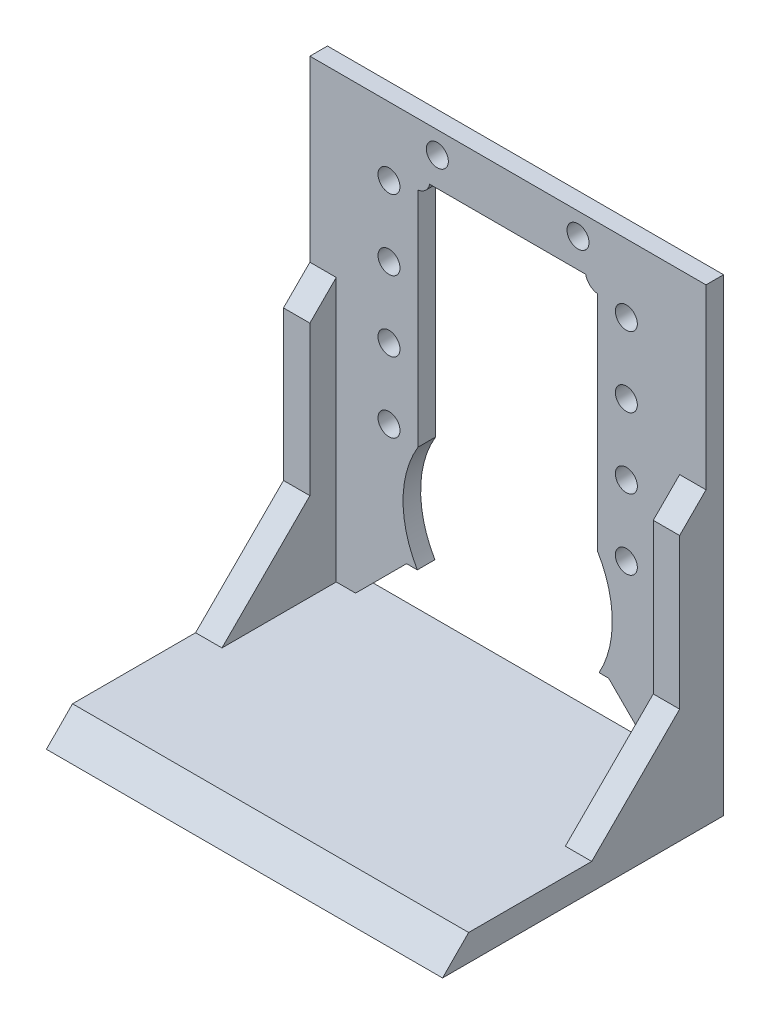
SolidWorks part; units mm, degrees
ref_plane "Płaszczyzna przednia" through (0, 0, 0) normal (0, 0, 1) x (1, 0, 0)
ref_plane "Płaszczyzna górna" through (0, 0, 0) normal (0, 1, 0) x (1, 0, 0)
ref_plane "Płaszczyzna prawa" through (0, 0, 0) normal (1, 0, 0) x (0, 0, -1)
sketch "Szkic2" plane through (0, 0, 0) normal (0, 0, 1) x (1, 0, 0)
  line L0 (-303.4601, 62.9953) -> (-191.4601, 62.9953)
  line L1 (-212.7368, 18.4953) -> (-237.0601, 18.7117)
  line L2 (-257.7368, 18.4953) -> (-282.1834, 18.4953)
  line L56 (-211.3394, 57.1953) -> (-193.5808, 57.1953)
  line L57 (-192.2601, 55.9583) -> (-192.2601, 30.6247)
  line L58 (-192.1834, 18.4953) -> (-191.4601, 18.4953)
  line L59 (-191.4601, 18.4953) -> (-186.4601, 23.4953)
  line L60 (-186.4601, 23.4953) -> (-186.4601, 57.9953)
  line L61 (-186.4601, 57.9953) -> (-191.4601, 62.9953)
  line L63 (-303.4601, 62.9953) -> (-308.4601, 57.9953)
  line L64 (-308.4601, 57.9953) -> (-308.4601, 23.4953)
  line L65 (-308.4601, 23.4953) -> (-303.4601, 18.4953)
  line L66 (-303.4601, 18.4953) -> (-302.7368, 18.4953)
  line L67 (-302.6601, 30.6247) -> (-302.6601, 55.9583)
  line L68 (-301.3394, 57.1953) -> (-283.5808, 57.1953)
  line L69 (-282.2601, 55.9583) -> (-282.2601, 30.6247)
  line L71 (-257.6601, 30.6247) -> (-257.6601, 55.9583)
  line L72 (-256.3394, 57.1953) -> (-238.5808, 57.1953)
  line L73 (-237.2601, 55.9583) -> (-237.2601, 30.6247)
  line L75 (-212.6601, 30.6247) -> (-212.6601, 55.9583)
  circle A2 centre (-300.4601, 60.4953) radius 1.25
  circle A4 centre (-305.9601, 55.2453) radius 1.25
  circle A6 centre (-305.9601, 47.2453) radius 1.25
  circle A8 centre (-305.9601, 39.2453) radius 1.25
  circle A10 centre (-305.9601, 31.2453) radius 1.25
  circle A12 centre (-278.9601, 31.2453) radius 1.25
  circle A14 centre (-278.9601, 39.2453) radius 1.25
  circle A16 centre (-278.9601, 47.2453) radius 1.25
  circle A18 centre (-278.9601, 55.2453) radius 1.25
  circle A20 centre (-284.4601, 60.4953) radius 1.25
  circle A22 centre (-255.4601, 60.4953) radius 1.25
  circle A24 centre (-260.9601, 55.2453) radius 1.25
  circle A26 centre (-260.9601, 47.2453) radius 1.25
  circle A28 centre (-260.9601, 39.2453) radius 1.25
  circle A30 centre (-260.9601, 31.2453) radius 1.25
  circle A32 centre (-233.9601, 31.2453) radius 1.25
  circle A34 centre (-233.9601, 39.2453) radius 1.25
  circle A36 centre (-233.9601, 47.2453) radius 1.25
  circle A38 centre (-233.9601, 55.2453) radius 1.25
  circle A40 centre (-239.4601, 60.4953) radius 1.25
  circle A42 centre (-210.4601, 60.4953) radius 1.25
  circle A44 centre (-215.9601, 55.2453) radius 1.25
  circle A46 centre (-215.9601, 47.2453) radius 1.25
  circle A48 centre (-215.9601, 39.2453) radius 1.25
  circle A50 centre (-215.9601, 31.2453) radius 1.25
  circle A52 centre (-188.9601, 31.2453) radius 1.25
  circle A54 centre (-188.9601, 39.2453) radius 1.25
  circle A56 centre (-188.9601, 47.2453) radius 1.25
  circle A58 centre (-188.9601, 55.2453) radius 1.25
  circle A60 centre (-194.4601, 60.4953) radius 1.25
  arc A84 (-212.6601, 55.9583) -> (-211.3394, 57.1953) centre (-212.8601, 57.4953) ccw
  arc A85 (-193.5808, 57.1953) -> (-192.2601, 55.9583) centre (-192.0601, 57.4953) ccw
  arc A86 (-192.1834, 18.4953) -> (-192.2601, 30.6247) centre (-202.4601, 24.4953) ccw
  arc A87 (-302.6601, 30.6247) -> (-302.7368, 18.4953) centre (-292.4601, 24.4953) ccw
  arc A88 (-302.6601, 55.9583) -> (-301.3394, 57.1953) centre (-302.8601, 57.4953) ccw
  arc A89 (-283.5808, 57.1953) -> (-282.2601, 55.9583) centre (-282.0601, 57.4953) ccw
  arc A90 (-282.1834, 18.4953) -> (-282.2601, 30.6247) centre (-292.4601, 24.4953) ccw
  arc A91 (-257.6601, 30.6247) -> (-257.7368, 18.4953) centre (-247.4601, 24.4953) ccw
  arc A92 (-257.6601, 55.9583) -> (-256.3394, 57.1953) centre (-257.8601, 57.4953) ccw
  arc A93 (-238.5808, 57.1953) -> (-237.2601, 55.9583) centre (-237.0601, 57.4953) ccw
  arc A94 (-237.1834, 18.4953) -> (-237.2601, 30.6247) centre (-247.4601, 24.4953) ccw
  arc A95 (-212.6601, 30.6247) -> (-212.7368, 18.4953) centre (-202.4601, 24.4953) ccw
  dimension "D2" = 11.9
  dimension "D1" = 45
  dimension "D3" = 45
extrude "Dodanie-wyciągnięcie2" add sketch "Szkic2" along normal blind 2 contours A95 L75 A84 L56 A85 L57 A86 L58 L59 L60 L61 L0 L63 L64 L65 L66 A87 L67 A88 L68 A89 L69 A90 L2 A91 L71 A92 L72 A93 L73 A94 L1 A60 A58 A56 A54 A52 A50 A48 A46 A44
sketch "Szkic3" plane through (0, 0, 2) normal (0, 0, 1) x (1, 0, 0)
  line L0 (-278.9601, 31.2453) -> (-260.9601, 31.2453)
  line L1 (-233.9601, 31.2453) -> (-215.9601, 31.2453)
  line L3 (-257.7368, 18.4953) -> (-282.1834, 18.4953) construction
  line L6 (-212.7368, 18.4953) -> (-237.0601, 18.7117) construction
  line L8 (-227.8984, 9.8035) -> (-221.8984, 9.8035)
  line L9 (-266.9601, 9.6953) -> (-272.9601, 9.6953)
  line L10 (-272.9601, 9.6953) -> (-272.9601, 18.4953)
  line L11 (-266.9601, 9.6953) -> (-266.9601, 18.4953)
  line L12 (-227.8984, 9.8035) -> (-227.8984, 18.6035)
  line L13 (-221.8984, 9.8035) -> (-221.8984, 18.5768)
  line L14 (-266.9601, 12.6953) -> (-272.9601, 12.6953)
  line L15 (-227.8984, 12.8035) -> (-221.8984, 12.8035)
  line L18 (-272.9601, 18.4953) -> (-272.9601, 42.6953)
  line L19 (-272.9601, 42.6953) -> (-266.9601, 42.6953)
  line L20 (-266.9601, 42.6953) -> (-266.9601, 18.4953)
  line L21 (-227.8984, 18.6035) -> (-227.8984, 42.8035)
  line L22 (-227.8984, 42.8035) -> (-221.8984, 42.8035)
  line L23 (-221.8984, 42.8035) -> (-221.8984, 18.5768)
  dimension "D1" = 30
  dimension "D2" = 30
  dimension "D3" = 6
  dimension "D4" = 6
  dimension "D5" = 3
  dimension "D6" = 3
extrude "Dodanie-wyciągnięcie3" add sketch "Szkic3" along normal blind 3 and the other way blind 2
sketch "Szkic4" plane through (0, 0, 2) normal (0, 0, 1) x (1, 0, 0)
  line L1 (-272.9601, 12.6953) -> (-266.9601, 12.6953)
  line L2 (-272.9601, 12.6953) -> (-272.9601, 9.6953)
  line L3 (-272.9601, 9.6953) -> (-266.9601, 9.6953)
  line L4 (-266.9601, 12.6953) -> (-266.9601, 9.6953)
  line L5 (-227.8984, 12.8035) -> (-221.8984, 12.8035)
  line L6 (-227.8984, 12.8035) -> (-227.8984, 9.8035)
  line L7 (-227.8984, 9.8035) -> (-221.8984, 9.8035)
  line L8 (-221.8984, 12.8035) -> (-221.8984, 9.8035)
extrude "Dodanie-wyciągnięcie4" add sketch "Szkic4" along normal blind 30 and the other way blind 2
chamfer "Sfazowanie1" distance 8 angle 45 4 edges at (-272.9601, 18.4953, 1) (-227.8984, 18.6302, 1) (-221.8984, 18.5768, 1) (-266.9601, 18.4953, 1)
chamfer "Sfazowanie2" distance 10 angle 45 2 edges at (-224.8984, 12.8035, 5) (-269.9601, 12.6953, 5)
chamfer "Sfazowanie3" distance 3 angle 45 4 edges at (-224.8984, 12.8035, 32) (-269.9601, 12.6953, 32) (-224.8984, 42.8035, 5) (-269.9601, 42.6953, 5)
sketch "Szkic5" plane through (0, 0, 2) normal (0, 0, 1) x (1, 0, 0)
  line L0 (-269.9601, 9.6953) -> (-269.9601, 62.9953)
  line L1 (-272.9601, 9.6953) -> (-266.9601, 9.6953) construction
  line L2 (-303.4601, 62.9953) -> (-191.4601, 62.9953) construction
  line L3 (-224.8984, 9.8035) -> (-224.8984, 62.9953)
  line L4 (-227.8984, 9.8035) -> (-221.8984, 9.8035) construction
  line L7 (-269.9601, 9.6953) -> (-308.4601, 9.6953)
  line L8 (-308.4601, 9.6953) -> (-308.4601, 62.9953)
  line L9 (-308.4601, 62.9953) -> (-269.9601, 62.9953)
  line L10 (-224.8984, 62.9953) -> (-186.4601, 62.9953)
  line L11 (-186.4601, 62.9953) -> (-186.4601, 9.8035)
  line L12 (-186.4601, 9.8035) -> (-224.8984, 9.8035)
extrude "Wytnij-wyciągnięcie1" cut sketch "Szkic5" against normal mid plane 97
sketch "Szkic6" plane through (-266.9601, 0, 0) normal (1, 0, 0) x (0, 0, -1)
  line L0 (-32, 9.6953) -> (-29, 12.6953)
  line L1 (-29, 12.6953) -> (0, 12.6953)
  line L2 (0, 12.6953) -> (0, 9.6953)
  line L3 (0, 9.6953) -> (-32, 9.6953)
extrude "Dodanie-wyciągnięcie5" add sketch "Szkic6" along normal up to surface (42.0617 mm away) up to face at (-224.8984, 30.735, 10)
sketch "Szkic7" plane through (-269.9601, 0, 0) normal (-1, 0, 0) x (0, 0, 1)
  line L0 (5, 22.6953) -> (5, 31.4277)
  line L1 (5, 22.6953) -> (5, 39.6953) construction
  line L2 (5, 31.4277) -> (32, 31.4277)
  line L3 (32, 31.4277) -> (32, 9.6643)
  line L4 (32, 9.6643) -> (29, 12.6953)
  line L5 (29, 12.6953) -> (15, 12.6953)
  line L6 (29, 12.6953) -> (2, 12.6953) construction
  line L7 (29, 12.6953) -> (15, 12.6953) construction
  line L8 (15, 12.6953) -> (5, 22.6953)
extrude "Wytnij-wyciągnięcie2" cut sketch "Szkic7" against normal mid plane 101
